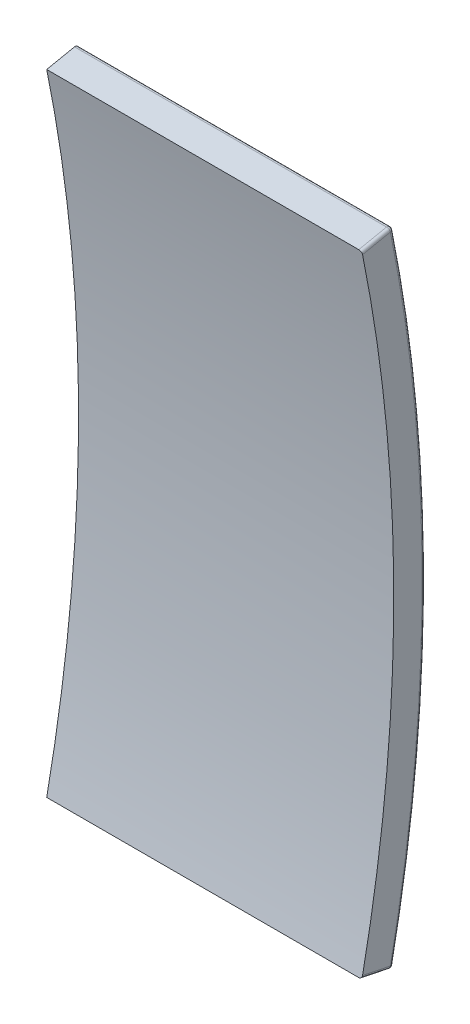
SolidWorks part; units mm, degrees
ref_plane "Front Plane" through (0, 0, 0) normal (0, 0, 1) x (1, 0, 0)
ref_plane "Top Plane" through (0, 0, 0) normal (0, 1, 0) x (1, 0, 0)
ref_plane "Right Plane" through (0, 0, 0) normal (1, 0, 0) x (0, 0, -1)
sketch "airflap" plane through (0, 0, 0) normal (1, 0, 0) x (0, 0, -1)
  line L0 (0, 0) -> (0, 50) construction
  line L1 (0, 0) -> (0, -50) construction
  line L2 (49.9696, 10.2) -> (48.9898, 10)
  line L3 (-48.9898, -10) -> (48.9898, -10) construction
  line L4 (-48.9898, -10) -> (-48.9898, 10) construction
  line L5 (-48.9898, 10) -> (48.9898, 10) construction
  line L6 (48.9898, -10) -> (48.9898, 10) construction
  line L7 (-48.9898, -10) -> (48.9898, 10) construction
  line L8 (-48.9898, 10) -> (48.9898, -10) construction
  line L9 (48.9898, -10) -> (49.9696, -10.2)
  arc A0 (48.9898, 10) -> (48.9898, -10) centre (0, 0) cw
  arc A1 (49.9696, 10.2) -> (49.9696, -10.2) centre (0, 0) cw
  dimension "D2" = 20
  dimension "D3" = 50
  dimension "D4" = 51
  dimension "D1" = 50
extrude "Boss-Extrude1" add sketch "airflap" along normal blind 10
fillet "Fillet3" radius 0.1 5 edges at (10, 10.1, -49.4797) (10, -10.1, -49.4797) (5, -10.2, -49.9696) (5, 10.2, -49.9696) (10, 0, -51)
